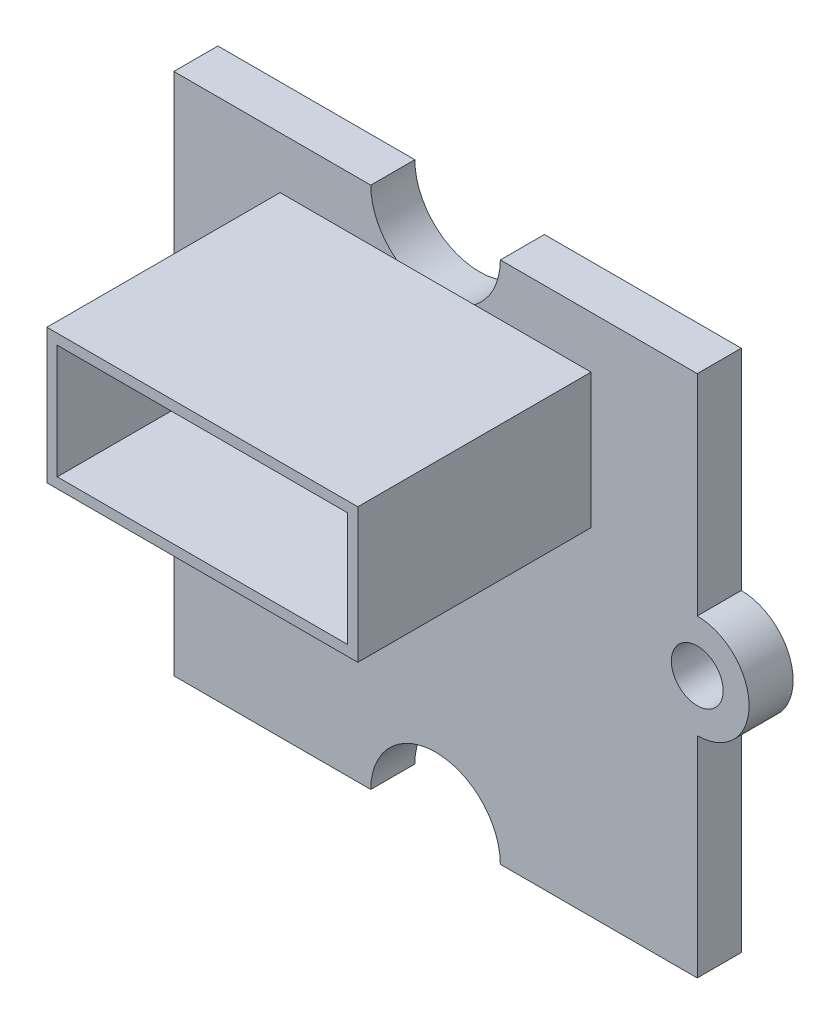
SolidWorks part; units mm, degrees
ref_plane "Alzado" through (0, 0, 0) normal (0, 0, 1) x (1, 0, 0)
ref_plane "Planta" through (0, 0, 0) normal (0, 1, 0) x (1, 0, 0)
ref_plane "Vista lateral" through (0, 0, 0) normal (1, 0, 0) x (0, 0, -1)
sketch "Croquis1" plane through (0, 0, 0) normal (0, 0, 1) x (1, 0, 0)
  line L0 (-2.5, 10.1) -> (-10.1, 10.1)
  line L1 (10.1, -10.1) -> (2.5, -10.1)
  line L2 (10.1, -10.1) -> (10.1, -2)
  line L3 (10.1, 10.1) -> (2.5, 10.1)
  line L4 (-10.1, -10.1) -> (-10.1, -2)
  line L5 (10.1, -10.1) -> (-10.1, 10.1) construction
  line L6 (10.1, 10.1) -> (-10.1, -10.1) construction
  line L7 (-2.5, -10.1) -> (-10.1, -10.1)
  line L8 (-10.1, 2) -> (-10.1, 10.1)
  line L9 (10.1, 2) -> (10.1, 10.1)
  arc A0 (-2.5, 10.1) -> (2.5, 10.1) centre (0, 10.1) ccw
  arc A1 (2.5, -10.1) -> (-2.5, -10.1) centre (0, -10.1) ccw
  arc A2 (-10.1, 2) -> (-10.1, -2) centre (-10.1, 0) ccw
  arc A3 (10.1, -2) -> (10.1, 2) centre (10.1, 0) ccw
  circle A4 centre (-10.1, 0) radius 1
  circle A5 centre (10.1, 0) radius 1
  point P0 (0, 0)
  point P13 (-9.9356, 2)
  point P17 (0, 0)
  point P22 (0, 0)
  point P23 (0, 0)
  dimension "D3" = 5
  dimension "D4" = 4
  dimension "D5" = 2
  dimension "D1" = 20.2
  dimension "D2" = 20.2
extrude "Saliente-Extruir1" add sketch "Croquis1" along normal blind 1.7
sketch "Croquis2" plane through (0, 0, 1.7) normal (0, 0, 1) x (1, 0, 0)
  line L0 (0, 7.6) -> (0, -7.6) construction
  line L1 (-2.5, 10.1) -> (-10.1, 10.1) construction
  line L2 (6, 2.9) -> (-6, 2.9)
  line L3 (6, 2.9) -> (6, 8.1)
  line L4 (6, 8.1) -> (-6, 8.1)
  line L5 (-6, 2.9) -> (-6, 8.1)
  line L6 (6, 2.9) -> (-6, 8.1) construction
  line L7 (6, 8.1) -> (-6, 2.9) construction
  line L8 (-5.6, 3.3) -> (-5.6, 7.7)
  line L9 (5.6, 7.7) -> (-5.6, 7.7)
  line L10 (5.6, 3.3) -> (5.6, 7.7)
  line L11 (5.6, 3.3) -> (-5.6, 3.3)
  arc A0 (-2.5, 10.1) -> (2.5, 10.1) centre (0, 10.1) ccw construction
  arc A1 (2.5, -10.1) -> (-2.5, -10.1) centre (0, -10.1) ccw construction
  point P8 (0, 5.5)
  dimension "D1" = 5.2
  dimension "D2" = 12
  dimension "D3" = 2
  dimension "D4" = 0.4
extrude "Saliente-Extruir2" add sketch "Croquis2" along normal blind 9
